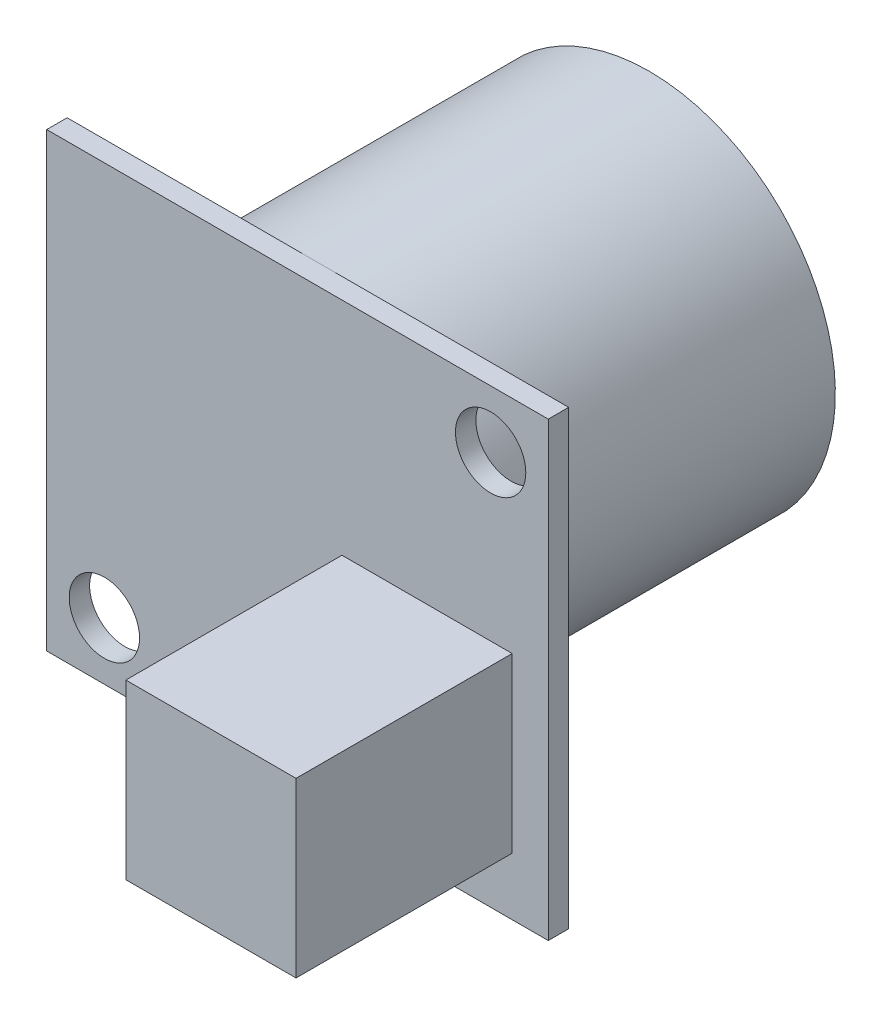
SolidWorks part; units mm, degrees
ref_plane "Front Plane" through (0, 0, 0) normal (0, 0, 1) x (1, 0, 0)
ref_plane "Top Plane" through (0, 0, 0) normal (0, 1, 0) x (1, 0, 0)
ref_plane "Right Plane" through (0, 0, 0) normal (1, 0, 0) x (0, 0, -1)
sketch "Sketch2" plane through (0, 0, 0) normal (0, 0, 1) x (1, 0, 0)
  line L1 (-11.05, -9.95) -> (11.05, -9.95)
  line L2 (-11.05, -9.95) -> (-11.05, 9.95)
  line L3 (-11.05, 9.95) -> (11.05, 9.95)
  line L4 (11.05, -9.95) -> (11.05, 9.95)
  line L5 (-11.05, -9.95) -> (11.05, 9.95) construction
  line L6 (-11.05, 9.95) -> (11.05, -9.95) construction
  circle A0 centre (-8.51, -7.41) radius 1.55
  circle A1 centre (8.51, 7.41) radius 1.55
  point P0 (0, 0)
  dimension "D3" = 3.1
  dimension "D7" = 3.1
  dimension "D1" = 22.1
  dimension "D2" = 19.9
  dimension "D4" = 2.54
  dimension "D5" = 2.54
  dimension "D6" = 2.54
  dimension "D8" = 2.54
extrude "Boss-Extrude1" add sketch "Sketch2" along normal blind 0.9 contours A1 | A0 | L2 L3 L4 L1 region at (-8.51, -7.41, 0) region at (8.51, 7.41, 0)
sketch "Sketch3" plane through (0, 0, 0.9) normal (0, 0, 1) x (1, 0, 0)
  line L0 (-11.05, -9.95) -> (11.05, -9.95) construction
  line L1 (1.9602, 0.21) -> (9.4602, 0.21)
  line L2 (1.9602, 0.21) -> (1.9602, -7.41)
  line L3 (1.9602, -7.41) -> (9.4602, -7.41)
  line L4 (9.4602, 0.21) -> (9.4602, -7.41)
  dimension "D1" = 7.5
  dimension "D2" = 7.62
  dimension "D3" = 2.54
extrude "Boss-Extrude2" add sketch "Sketch3" along normal blind 9.525
sketch "Sketch4" plane through (0, 0, 0) normal (0, 0, -1) x (-1, 0, 0)
  line L0 (11.05, 9.95) -> (-11.05, 9.95) construction
  line L2 (-11.05, 1.75) -> (11.05, 1.75) construction
  line L3 (-11.05, -9.95) -> (-11.05, 9.95) construction
  line L4 (11.05, -9.95) -> (11.05, 9.95) construction
  circle A0 centre (0, 1.75) radius 8.2
  point P10 (0, 0)
  point P11 (0, 0)
  point P12 (0, 1.75)
  dimension "D1" = 16.4
extrude "Boss-Extrude3" add sketch "Sketch4" along normal blind 14.6 contours A0
